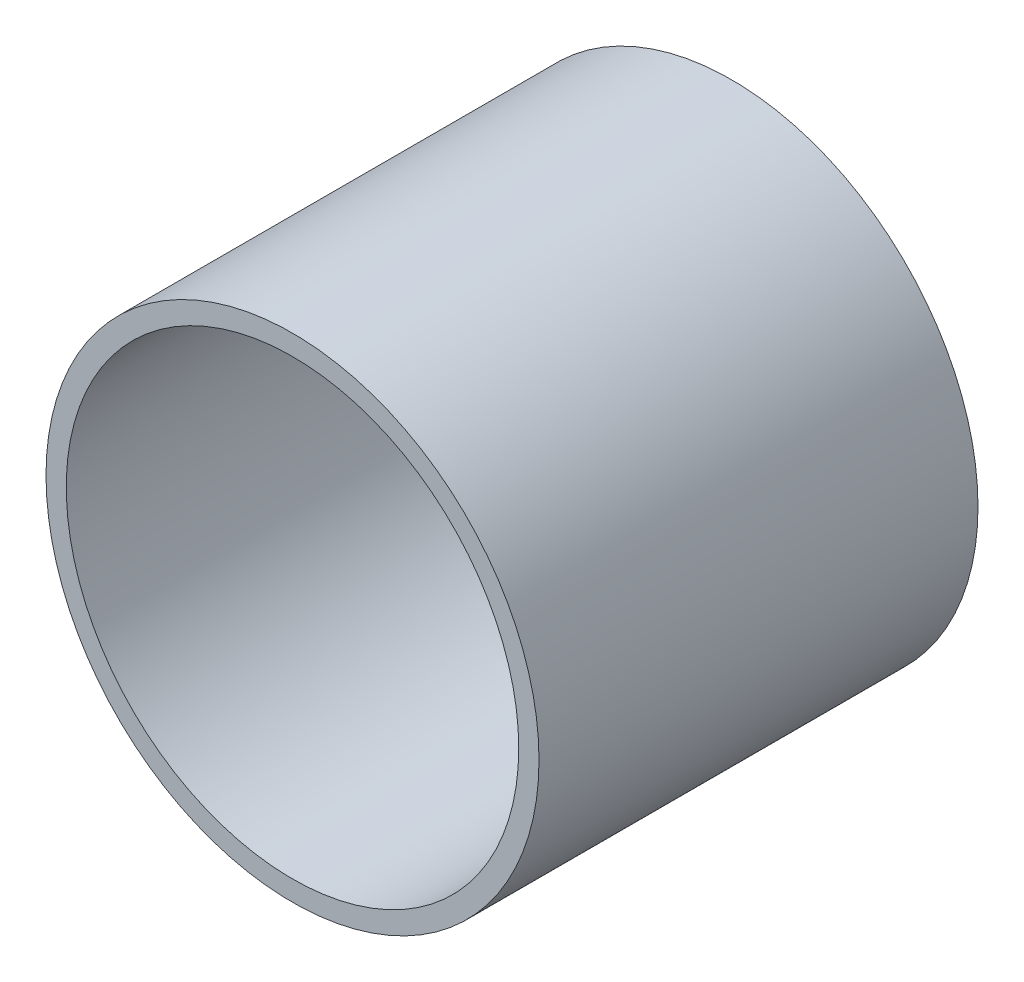
SolidWorks part; units mm, degrees
ref_plane "Plano frontal" through (0, 0, 0) normal (0, 0, 1) x (1, 0, 0)
ref_plane "Plano superior" through (0, 0, 0) normal (0, 1, 0) x (1, 0, 0)
ref_plane "Plano direito" through (0, 0, 0) normal (1, 0, 0) x (0, 0, -1)
sketch "Esboço1" plane through (0, 0, 0) normal (0, 0, 1) x (1, 0, 0)
  circle A0 centre (0, 0) radius 33.5
  circle A1 centre (0, 0) radius 36.5
  dimension "D2" = 73
  dimension "D1" = 3
extrude "Ressalto-extrusão1" add sketch "Esboço1" along normal blind 65
extrude "Ressalto-extrusão2" add sketch "Esboço1<3>" along normal blind 3 contours A0 region at (0, 0, 0)
sketch "Esboço1<3>" plane through (0, 0, 0) normal (0, 0, 1) x (1, 0, 0) same geometry as "Esboço1"
